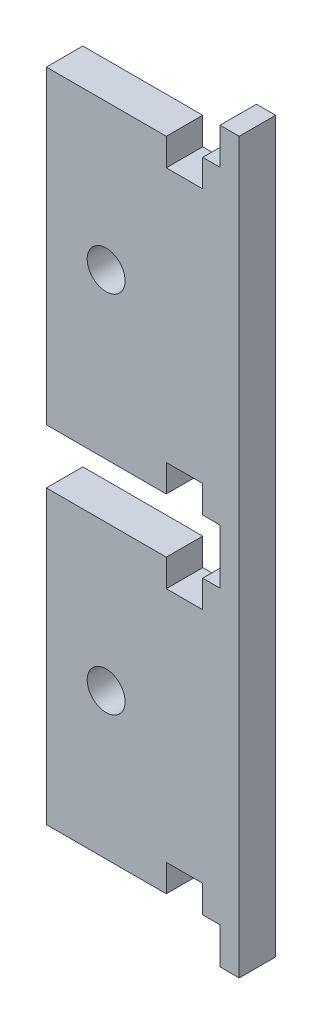
SolidWorks part; units mm, degrees
material "AISI 4130 Steel, annealed at 865C"
ref_plane "X-Y Datum" through (0, 0, 0) normal (0, 0, 1) x (1, 0, 0)
ref_plane "X-Z Datum" through (0, 0, 0) normal (0, 1, 0) x (1, 0, 0)
ref_plane "Y-Z Datum" through (0, 0, 0) normal (1, 0, 0) x (0, 0, -1)
sketch "Sketch2" plane through (0, 0, 0) normal (0, 0, 1) x (1, 0, 0)
  line L0 (34.925, 127) -> (0, 127) construction
  line L1 (0, 0) -> (40.64, 0)
  line L2 (0, 0) -> (0, 127)
  line L3 (0, 127) -> (40.64, 127)
  line L4 (40.64, 0) -> (40.64, 127)
  point P7 (17.4625, 31.75)
  point P8 (17.4625, 95.25)
  dimension "D1" = 40.64
extrude "Boss-Extrude1" add sketch "Sketch2" along normal blind 6.35
hole_wizard "M6 Clearance Hole1" positions "Sketch3" profile "Sketch4" hole size "M6" standard "ANSI Metric" end condition through all
sketch "Sketch3" plane through (0, 0, 6.35) normal (0, 0, 1) x (1, 0, 0)
  point P0 (17.4625, 31.75)
  point P3 (17.4625, 95.25)
sketch "Sketch4" plane through (17.4625, 31.75, 6.35) normal (1, 0, 0) x (0, -1, 0)
  line L0 (0, 0) -> (0, 6.35)
  line L1 (0, 6.35) -> (3.3, 6.35)
  line L2 (3.3, 6.35) -> (3.3, 0)
  line L5 (3.3, 0) -> (0, 0)
  line L11 (0, -6.35) -> (0, 107.95) construction
  dimension "Thru Hole Dia." = 6.6
  dimension "Thru Hole Depth" = 6.35
sketch "Sketch5" plane through (0, 0, 6.35) normal (0, 0, 1) x (1, 0, 0)
  line L0 (7.0505, 127) -> (7.0505, 0)
  line L1 (40.64, 127) -> (0, 127) construction
  line L2 (0, 0) -> (40.64, 0) construction
  circle A0 centre (17.4625, 95.25) radius 3.3 construction
  point P6 (14.1625, 95.25)
  line M4 (0, 127) -> (0, 0)
  line M5 (0, 0) -> (40.64, 0)
  line M7 (40.64, 127) -> (0, 127)
  dimension "D1" = 7.112
extrude "Cut-Extrude1" cut sketch "Sketch5" against normal through all and the other way through all contours L0 M7 M4 M5 region at (3.5253, 63.5, 6.35)
sketch "Sketch6" plane through (0, 0, 6.35) normal (0, 0, 1) x (1, 0, 0)
  line L0 (-3.175, 120.65) -> (38.1, 120.65)
  line L1 (38.1, 120.65) -> (38.1, 130.175)
  line L2 (38.1, 130.175) -> (-3.175, 130.175)
  line L3 (-3.175, 130.175) -> (-3.175, 120.65)
  line L4 (0, 123.825) -> (34.925, 123.825)
  line L5 (34.925, 123.825) -> (34.925, 127)
  line L6 (34.925, 127) -> (0, 127)
  line L7 (0, 127) -> (0, 123.825)
  line L8 (0, 123.825) -> (34.925, 123.825)
  line L9 (34.925, 123.825) -> (34.925, 127)
  line L10 (34.925, 127) -> (0, 127)
  line L11 (0, 127) -> (0, 123.825)
  line L12 (0, 60.325) -> (34.925, 60.325)
  line L13 (34.925, 60.325) -> (34.925, 63.5)
  line L14 (34.925, 63.5) -> (0, 63.5)
  line L15 (0, 63.5) -> (0, 60.325)
  line L16 (0, 60.325) -> (34.925, 60.325)
  line L17 (34.925, 60.325) -> (34.925, 63.5)
  line L18 (34.925, 63.5) -> (0, 63.5)
  line L19 (0, 63.5) -> (0, 60.325)
  line L24 (0, 0) -> (34.925, 0)
  line L25 (34.925, 0) -> (34.925, 3.175)
  line L26 (34.925, 3.175) -> (0, 3.175)
  line L27 (0, 3.175) -> (0, 0)
  line L28 (38.1, 66.675) -> (-3.175, 66.675)
  line L29 (-3.175, 66.675) -> (-3.175, 57.15)
  line L30 (-3.175, 57.15) -> (38.1, 57.15)
  line L31 (38.1, 57.15) -> (38.1, 66.675)
  line L32 (38.1, 6.35) -> (-3.175, 6.35)
  line L33 (-3.175, 6.35) -> (-3.175, -3.175)
  line L34 (-3.175, -3.175) -> (38.1, -3.175)
  line L35 (38.1, -3.175) -> (38.1, 6.35)
  line L36 (37.3062, 127) -> (37.3063, 0)
  line L37 (40.64, 127) -> (7.0505, 127) construction
  line L38 (7.0505, 0) -> (40.64, 0) construction
  line M19 (7.0505, 127) -> (7.0505, 0)
  line M20 (7.0505, 0) -> (40.64, 0)
  line M22 (40.64, 127) -> (7.0505, 127)
  dimension "D5" = 2.3813
  dimension "D1" = 0
  dimension "D2" = 0
  dimension "D4" = 3.175
extrude "Cut-Extrude2" cut sketch "Sketch6" against normal through all contours L36 L9 L8 L0 M22 M19 | L8 L9 M22 M19 | L36 L28 L18 L17 L16 L30 M19 | L17 L18 L16 M19 | L36 L32 L26 L25 M19 M20 | L25 L26 M19 M20 region at (23.1953, 122.4692, 6.35) region at (20.9877, 125.4125, 6.35) region at (22.1784, 66.3578, 6.35) region at (20.9878, 61.9125, 6.35) region at (23.1953, 4.5308, 6.35) region at (20.9878, 1.5875, 6.35)
sketch "Sketch7" plane through (0, 0, 6.35) normal (0, 0, 1) x (1, 0, 0)
  line L18 (34.29, 120.65) -> (27.94, 120.65)
  line L19 (34.29, 120.65) -> (34.29, 115.8875)
  line L20 (34.29, 115.8875) -> (27.94, 115.8875)
  line L21 (27.94, 120.65) -> (27.94, 115.8875)
  line L22 (34.29, 71.4375) -> (27.94, 71.4375)
  line L23 (34.29, 71.4375) -> (34.29, 66.675)
  line L24 (34.29, 66.675) -> (27.94, 66.675)
  line L25 (27.94, 71.4375) -> (27.94, 66.675)
  line L26 (34.29, 57.15) -> (27.94, 57.15)
  line L27 (34.29, 57.15) -> (34.29, 52.3875)
  line L28 (34.29, 52.3875) -> (27.94, 52.3875)
  line L29 (27.94, 57.15) -> (27.94, 52.3875)
  line L30 (34.29, 11.1125) -> (27.94, 11.1125)
  line L31 (34.29, 11.1125) -> (34.29, 6.35)
  line L32 (34.29, 6.35) -> (27.94, 6.35)
  line L33 (27.94, 11.1125) -> (27.94, 6.35)
extrude "Cut-Extrude3" cut sketch "Sketch7" against normal through all
